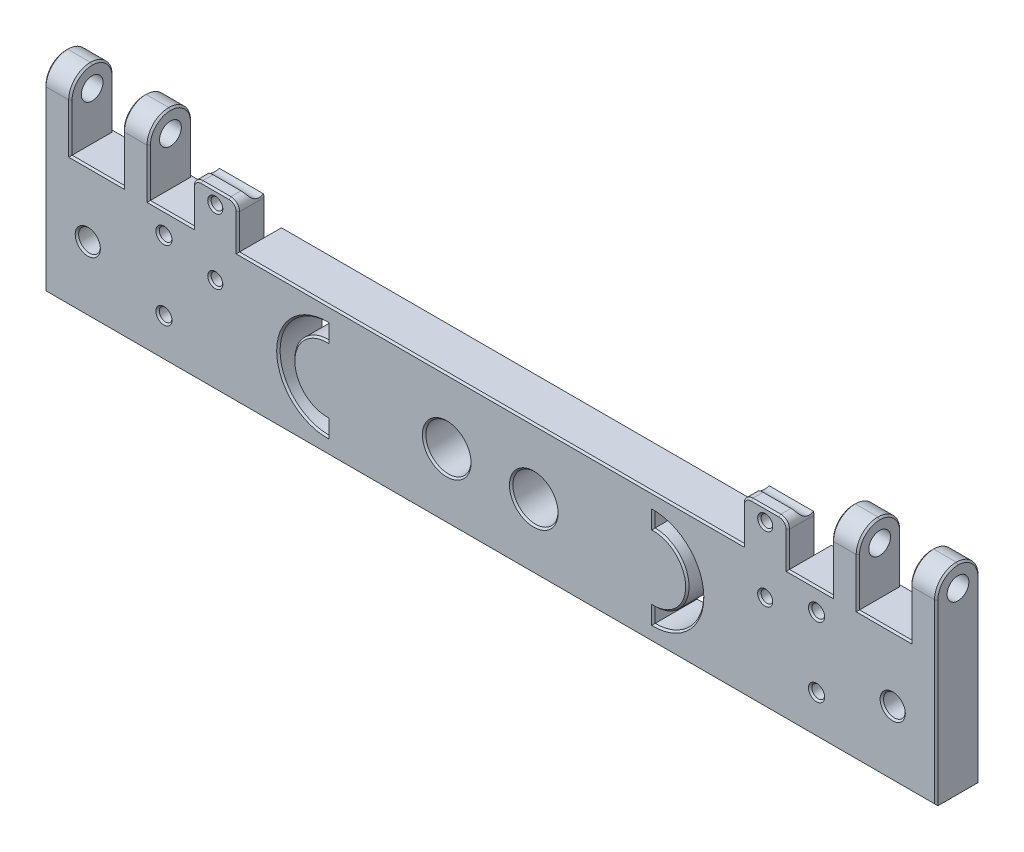
SolidWorks part; units mm, degrees
ref_plane "Front Plane" through (0, 0, 0) normal (0, 0, 1) x (1, 0, 0)
ref_plane "Top Plane" through (0, 0, 0) normal (0, 1, 0) x (1, 0, 0)
ref_plane "Right Plane" through (0, 0, 0) normal (1, 0, 0) x (0, 0, -1)
sketch "Sketch1" plane through (0, 0, 0) normal (0, 0, 1) x (1, 0, 0)
  line L0 (0, 0) -> (0, 19.05) construction
  line L1 (-122.555, 19.05) -> (-107.315, 19.05)
  line L2 (-130.175, 19.05) -> (-130.175, -19.05)
  line L3 (-130.175, -19.05) -> (130.175, -19.05)
  line L4 (130.175, 19.05) -> (130.175, -19.05)
  line L5 (-130.175, 19.05) -> (130.175, -19.05) construction
  line L6 (-130.175, -19.05) -> (130.175, 19.05) construction
  line L7 (-80.264, 27.94) -> (-80.264, 8.89) construction
  line L8 (-81.28, 0) -> (-117.475, 0) construction
  line L9 (-130.175, 19.05) -> (-130.175, 39.37)
  line L10 (-130.175, 39.37) -> (-122.555, 39.37)
  line L11 (-122.555, 39.37) -> (-122.555, 19.05)
  line L12 (-114.935, 19.05) -> (-114.935, 39.37) construction
  line L13 (-107.315, 39.37) -> (-107.315, 19.05)
  line L14 (-99.695, 39.37) -> (-107.315, 39.37)
  line L15 (-99.695, 19.05) -> (-99.695, 39.37)
  line L16 (-99.695, 19.05) -> (-86.868, 19.05)
  line L17 (114.935, 19.05) -> (114.935, 39.37) construction
  line L18 (99.695, 19.05) -> (99.695, 39.37)
  line L19 (99.695, 39.37) -> (107.315, 39.37)
  line L20 (107.315, 39.37) -> (107.315, 19.05)
  line L21 (122.555, 39.37) -> (122.555, 19.05)
  line L22 (130.175, 39.37) -> (122.555, 39.37)
  line L23 (130.175, 19.05) -> (130.175, 39.37)
  line L24 (107.315, 19.05) -> (122.555, 19.05)
  line L25 (-86.868, 19.05) -> (-86.868, 29.21)
  line L26 (-84.328, 31.75) -> (-76.2, 31.75)
  line L27 (-73.66, 29.21) -> (-73.66, 19.05)
  line L28 (73.66, 29.21) -> (73.66, 19.05)
  line L29 (84.328, 31.75) -> (76.2, 31.75)
  line L30 (86.868, 19.05) -> (86.868, 29.21)
  line L31 (-73.66, 19.05) -> (73.66, 19.05)
  line L32 (86.868, 19.05) -> (99.695, 19.05)
  circle A0 centre (-117.475, 0) radius 3.175
  circle A1 centre (117.475, 0) radius 3.175
  circle A2 centre (-80.264, 27.94) radius 1.7
  circle A4 centre (-80.264, 8.89) radius 1.7
  circle A5 centre (80.264, 8.89) radius 1.7
  circle A6 centre (80.264, 27.94) radius 1.7
  circle A7 centre (-95.25, 12.7) radius 1.85
  circle A8 centre (-95.25, -7.62) radius 1.85
  circle A9 centre (95.25, -7.62) radius 1.85
  circle A10 centre (95.25, 12.7) radius 1.85
  arc A11 (86.868, 29.21) -> (84.328, 31.75) centre (84.328, 29.21) ccw
  arc A12 (73.66, 29.21) -> (76.2, 31.75) centre (76.2, 29.21) cw
  arc A13 (-73.66, 29.21) -> (-76.2, 31.75) centre (-76.2, 29.21) ccw
  arc A14 (-86.868, 29.21) -> (-84.328, 31.75) centre (-84.328, 29.21) cw
  point P0 (0, 0)
  point P50 (-80.264, 31.75)
  point P58 (86.868, 31.75)
  point P61 (73.66, 31.75)
  point P64 (-73.66, 31.75)
  point P67 (-86.868, 31.75)
  dimension "D1" = 6.35
  dimension "D6" = 3.4
  dimension "D9" = 3.7
  dimension "D10" = 190.5
  dimension "D18" = 2.54
  dimension "D2" = 260.35
  dimension "D3" = 12.7
  dimension "D4" = 38.1
  dimension "D5" = 19.05
  dimension "D7" = 80.264
  dimension "D8" = 12.7
  dimension "D11" = 15.24
  dimension "D12" = 20.32
  dimension "D13" = 7.62
  dimension "D14" = 20.32
  dimension "D15" = 27.94
  dimension "D16" = 13.208
  dimension "D17" = 12.7
extrude "Boss-Extrude1" add sketch "Sketch1" along normal blind 12.7
sketch "Sketch2" plane through (0, 0, 0) normal (0, 0, -1) x (-1, 0, 0)
  line L0 (0, 0) -> (0, 19.05) construction
  line L7 (-84.328, 31.75) -> (-76.2, 31.75) construction
  line L15 (73.66, 19.05) -> (73.66, 29.21) construction
  line L16 (-73.66, 29.21) -> (-73.66, 19.05) construction
  line L18 (-86.868, 19.05) -> (-86.868, 29.21) construction
  line L20 (73.66, 19.05) -> (86.868, 19.05) construction
  line L25 (-73.66, 29.21) -> (-73.66, 19.05)
  line L26 (-73.66, 19.05) -> (73.66, 19.05) construction
  line L28 (73.66, -19.05) -> (73.66, 19.05)
  line L29 (86.868, -19.05) -> (73.66, -19.05)
  line L30 (86.868, 19.05) -> (86.868, -19.05)
  line L31 (86.868, 19.05) -> (86.868, 29.21)
  line L32 (84.328, 31.75) -> (76.2, 31.75)
  line L33 (73.66, 29.21) -> (73.66, 19.05)
  line L35 (-84.328, 31.75) -> (-76.2, 31.75)
  line L36 (-86.868, 19.05) -> (-86.868, 29.21)
  line L37 (-86.868, 19.05) -> (-86.868, -19.05)
  line L38 (130.175, -19.05) -> (-130.175, -19.05) construction
  line L39 (-86.868, -19.05) -> (-73.66, -19.05)
  line L40 (-73.66, -19.05) -> (-73.66, 19.05)
  circle A0 centre (-47.625, 0) radius 6.6
  circle A1 centre (47.625, 0) radius 6.6
  arc A4 (-73.66, 29.21) -> (-76.2, 31.75) centre (-76.2, 29.21) ccw construction
  arc A5 (-84.328, 31.75) -> (-86.868, 29.21) centre (-84.328, 29.21) ccw construction
  arc A10 (84.328, 31.75) -> (86.868, 29.21) centre (84.328, 29.21) cw
  arc A11 (73.66, 29.21) -> (76.2, 31.75) centre (76.2, 29.21) cw
  arc A12 (-73.66, 29.21) -> (-76.2, 31.75) centre (-76.2, 29.21) ccw
  arc A13 (-84.328, 31.75) -> (-86.868, 29.21) centre (-84.328, 29.21) ccw
  dimension "D1" = 13.2
  dimension "D2" = 95.25
extrude "Cut-Extrude1" cut sketch "Sketch2" against normal blind 5.08
fillet "Fillet1" radius 6.35 8 edges at (-126.365, 39.37, 0) (-126.365, 39.37, 12.7) (-103.505, 39.37, 12.7) (-103.505, 39.37, 0) (103.505, 39.37, 0) (103.505, 39.37, 12.7) (126.365, 39.37, 12.7) (126.365, 39.37, 0)
sketch "Sketch3" plane through (130.175, 0, 0) normal (1, 0, 0) x (0, 0, -1)
  line L0 (0, 33.02) -> (-6.35, 33.02) construction
  line L1 (-6.35, 33.02) -> (-6.35, 39.37) construction
  circle A0 centre (-6.35, 33.02) radius 3.175
  arc A1 (-6.35, 39.37) -> (-12.7, 33.02) centre (-6.35, 33.02) ccw construction
  dimension "D1" = 6.35
extrude "Cut-Extrude2" cut sketch "Sketch3" against normal blind 325.374
sketch "Sketch4" plane through (0, 0, 12.7) normal (0, 0, 1) x (1, 0, 0)
  line L0 (0, 19.05) -> (0, -19.05) construction
  line L2 (-130.175, -19.05) -> (130.175, -19.05) construction
  line L3 (47.625, 14.22) -> (47.625, 9.91)
  line L4 (47.625, -9.91) -> (47.625, -14.22)
  line L5 (-47.625, -9.91) -> (-47.625, -14.22)
  line L6 (-47.625, 14.22) -> (-47.625, 9.91)
  line L7 (73.66, 19.05) -> (-73.66, 19.05) construction
  circle A0 centre (12.7, 0) radius 6.6
  circle A1 centre (-12.7, 0) radius 6.6
  arc A2 (47.625, -9.91) -> (47.625, 9.91) centre (47.625, 0) ccw
  circle A3 centre (47.625, 0) radius 6.6 construction
  arc A4 (47.625, -14.22) -> (47.625, 14.22) centre (47.625, 0) ccw
  arc A7 (-47.625, -14.22) -> (-47.625, 14.22) centre (-47.625, 0) cw
  arc A8 (-47.625, -9.91) -> (-47.625, 9.91) centre (-47.625, 0) cw
  dimension "D1" = 25.4
  dimension "D2" = 13.2
  dimension "D3" = 9.91
  dimension "D4" = 4.31
extrude "Cut-Extrude3" cut sketch "Sketch4" against normal blind 12.7
chamfer "Chamfer1" distance 0.5 angle 45 68 edges at (93.4, 12.7, 12.7) (-93.4, 12.7, 12.7) (78.564, 27.94, 12.7) (-78.564, 8.89, 12.7) (114.3, 0, 12.7) (-99.695, 26.035, 0) (99.695, 26.035, 0) (-99.695, 37.5101, 1.8599) (99.695, 37.5101, 1.8599) (-99.695, 37.5101, 10.8401) (99.695, 37.5101, 10.8401) (-99.695, 26.035, 12.7) (-93.2815, 19.05, 12.7) (99.695, 26.035, 12.7) (107.315, 26.035, 0) (122.555, 26.035, 0) (107.315, 37.5101, 1.8599) (122.555, 37.5101, 1.8599) (107.315, 37.5101, 10.8401) (122.555, 37.5101, 10.8401) (107.315, 26.035, 12.7) (114.935, 19.05, 12.7) (122.555, 26.035, 12.7) (130.175, 6.985, 0) (-130.175, 6.985, 0) (130.175, 37.5101, 1.8599) (-130.175, 37.5101, 1.8599) (130.175, 37.5101, 10.8401) (-130.175, 37.5101, 10.8401) (130.175, 6.985, 12.7) (0, -19.05, 12.7) (-130.175, 6.985, 12.7) (-107.315, 26.035, 0) (-122.555, 26.035, 0) (-107.315, 37.5101, 1.8599) (-122.555, 37.5101, 1.8599) (-107.315, 37.5101, 10.8401) (-122.555, 37.5101, 10.8401) (-107.315, 26.035, 12.7) (-114.935, 19.05, 12.7) (-122.555, 26.035, 12.7) (-114.3, 0, 12.7) (-78.564, 27.94, 12.7) (78.564, 8.89, 12.7) (-97.1, -7.62, 12.7) (97.1, -7.62, 12.7) (19.3, 0, 12.7) (-19.3, 0, 12.7) (-47.625, 12.065, 12.7) (-61.845, 0, 12.7) (-47.625, -12.065, 12.7) (-57.535, 0, 12.7) (47.625, -12.065, 12.7) (61.845, 0, 12.7) (47.625, 12.065, 12.7) (57.535, 0, 12.7) (-86.868, 24.13, 12.7) (-86.1241, 31.0061, 12.7) (-80.264, 31.75, 12.7) (-74.4039, 31.0061, 12.7) (-73.66, 24.13, 12.7) (0, 19.05, 12.7) (73.66, 24.13, 12.7) (74.4039, 31.0061, 12.7) (80.264, 31.75, 12.7) (86.1241, 31.0061, 12.7) (86.868, 24.13, 12.7) (93.2815, 19.05, 12.7)
